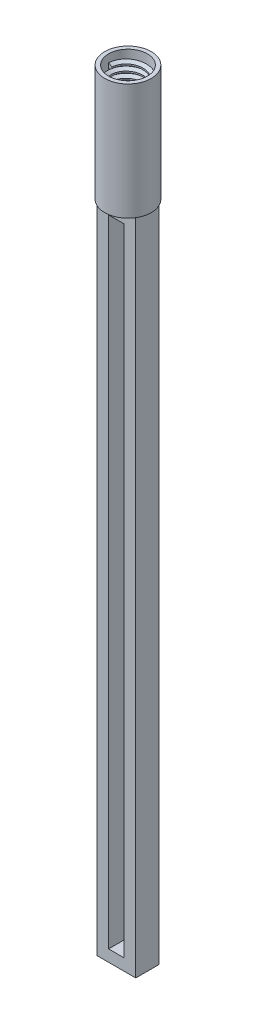
SolidWorks part; units mm, degrees
ref_plane "Ön Düzlem" through (0, 0, 0) normal (0, 0, 1) x (1, 0, 0)
ref_plane "Üst Düzlem" through (0, 0, 0) normal (0, 1, 0) x (1, 0, 0)
ref_plane "Sağ Düzlem" through (0, 0, 0) normal (1, 0, 0) x (0, 0, -1)
sketch "Çizim2" plane through (0, 0, 0) normal (0, 0, 1) x (1, 0, 0)
  line L0 (1.5, 1.5) -> (3.5, 1.5)
  line L1 (0, 0) -> (5, 0)
  line L2 (0, 0) -> (0, 85)
  line L3 (0, 85) -> (5, 85)
  line L4 (5, 0) -> (5, 85)
  line L5 (3.5, 1.5) -> (3.5, 83.5)
  line L6 (1.5, 83.5) -> (3.5, 83.5)
  line L7 (1.5, 1.5) -> (1.5, 83.5)
  dimension "D2" = 85
  dimension "D3" = 5
  dimension "D1" = 1.5
extrude "Yükseklik-Ekstrüzyon1" add sketch "Çizim2" along normal blind 3
sketch "Çizim3" plane through (0, 85, 0) normal (0, 1, 0) x (1, 0, 0)
  circle A0 centre (2.5, -1.5) radius 3
  dimension "D1" = 6
extrude "Yükseklik-Ekstrüzyon2" add sketch "Çizim3" along normal blind 15
sketch "Çizim4" plane through (0, 100, 0) normal (0, 1, 0) x (1, 0, 0)
  circle A0 centre (2.5, -1.5) radius 2.5
extrude "Kes-Ekstrüzyon1" cut sketch "Çizim4" against normal blind 10
thread "Diş1" pitch 0.8 method extrude profile "Diş Profili1" start angle 0, offset 1, length 10, pitch 0.8, diameter 5
ref_plane "Düzlem2" through (0, 99, 1.5) normal (0, 0, 1) x (-1, 0, 0)
sketch "Diş Profili1" plane through (0, 99, 1.5) normal (0, 0, 1) x (-1, 0, 0)
  line L0 (0, 0) -> (0, 0.8) construction
  line L11 (0, 0) -> (0, 0.7)
  line L12 (0, 0.7) -> (-0.433, 0.45)
  line L13 (-0.433, 0.45) -> (-0.433, 0.25)
  line L15 (-0.433, 0.25) -> (0, 0)
  line L17 (-0.433, 0.35) -> (0, 0.35) construction
  point P2 (0, 0)
  dimension "Pitch" = 0.8
  dimension "Profile_Angle" = 60
  dimension "Profile_Land" = 0.2
  dimension "Profile_Height" = 0.433
